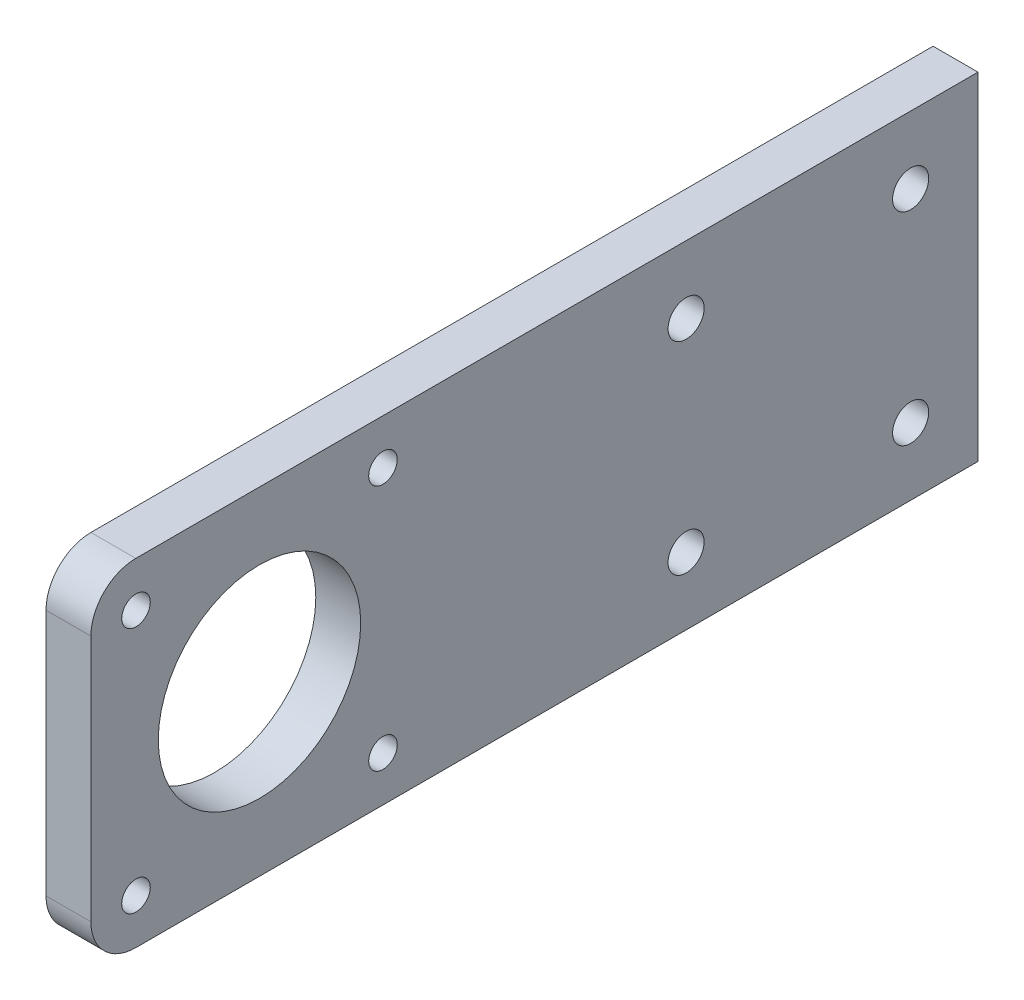
SolidWorks part; units mm, degrees
material "6061-T6 (SS)"
ref_plane "Front" through (0, 0, 0) normal (0, 0, 1) x (1, 0, 0)
ref_plane "Top" through (0, 0, 0) normal (0, 1, 0) x (1, 0, 0)
ref_plane "Right" through (0, 0, 0) normal (1, 0, 0) x (0, 0, -1)
sketch "Sketch1" plane through (0, 0, 0) normal (1, 0, 0) x (0, 0, -1)
  line L0 (0, -23.8379) -> (0, 23.8379)
  line L3 (0, 23.8379) -> (-125.4379, 23.8379)
  line L4 (-125.4379, -23.8379) -> (0, -23.8379)
  line L5 (-125.4379, 23.8379) -> (-125.4379, -23.8379)
  circle A1 centre (-101.6, 0) radius 14.3129
  point P4 (0, 0)
  dimension "D3" = 28.6258
  dimension "D1" = 9.525
  dimension "D5" = 101.6
extrude "Boss-Extrude1" add sketch "Sketch1" along normal blind 6.35
fillet "Fillet1" radius 6.35 2 edges at (3.175, -23.8379, 125.4379) (3.175, 23.8379, 125.4379)
sketch "Sketch4" plane through (0, 0, 0) normal (-1, 0, 0) x (0, 0, 1)
  point P0 (84.1375, 17.4625)
  point P3 (119.0625, 17.4625)
  point P6 (119.0625, -17.4625)
  point P9 (84.1375, -17.4625)
hole_wizard "#10-32 Tapped Hole1" positions "Sketch4" profile "Sketch3" tap size "#10-32" standard "ANSI Inch" end condition up to next
sketch "Sketch3" plane through (0, 17.4625, 84.1375) normal (0, 1, 0) x (0, 0, 1)
  line L0 (0, 0) -> (0, 6.35)
  line L1 (0, 6.35) -> (2.0193, 6.35)
  line L2 (2.0193, 6.35) -> (2.0193, 0)
  line L5 (2.0193, 0) -> (0, 0)
  line L11 (0, -6.35) -> (0, 107.95) construction
  dimension "Thru Tap Drill Dia." = 4.0386
  dimension "Thru Tap Drill Depth" = 6.35
cosmetic thread "Hole Thread1" parameters "D2"=4.826
cosmetic thread "Hole Thread2" parameters "D2"=4.826
cosmetic thread "Hole Thread3" parameters "D2"=4.826
cosmetic thread "Hole Thread4" parameters "D2"=4.826
sketch "Sketch7" plane through (6.35, 0, 0) normal (1, 0, 0) x (0, 0, -1)
  line L0 (-50.8, 23.8379) -> (-50.8, -23.8379) construction
  line L1 (0, 23.8379) -> (-119.0879, 23.8379) construction
  line L2 (-119.0879, -23.8379) -> (0, -23.8379) construction
  line L4 (0, -23.8379) -> (0, 23.8379) construction
  point P0 (-9.525, 14.3129)
  point P2 (-41.275, 14.3129)
  point P4 (-41.275, -14.3129)
  point P6 (-9.525, -14.3129)
  dimension "D1" = 50.8
  dimension "D2" = 9.525
  dimension "D3" = 9.525
  dimension "D4" = 9.525
  dimension "D5" = 9.525
hole_wizard "#10 Clearance Hole1" positions "Sketch7" profile "Sketch6" hole size "#10" standard "ANSI Inch" end condition up to next
sketch "Sketch6" plane through (6.35, 14.3129, 9.525) normal (0, 1, 0) x (0, 0, -1)
  line L0 (0, 0) -> (0, 6.35)
  line L1 (0, 6.35) -> (2.5527, 6.35)
  line L2 (2.5527, 6.35) -> (2.5527, 0)
  line L5 (2.5527, 0) -> (0, 0)
  line L11 (0, -6.35) -> (0, 107.95) construction
  dimension "Thru Hole Dia." = 5.1054
  dimension "Thru Hole Depth" = 6.35
